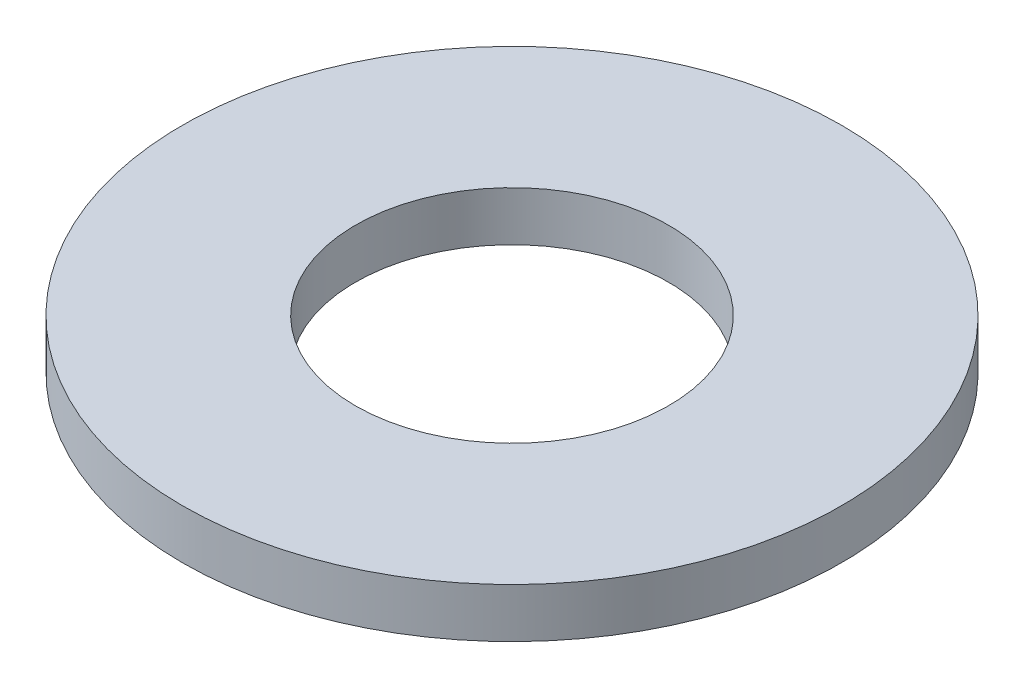
SolidWorks part; units mm, degrees
ref_plane "Front Plane" through (0, 0, 0) normal (0, 0, 1) x (1, 0, 0)
ref_plane "Top Plane" through (0, 0, 0) normal (0, 1, 0) x (1, 0, 0)
ref_plane "Right Plane" through (0, 0, 0) normal (1, 0, 0) x (0, 0, -1)
sketch "Sketch1" plane through (0, 0, 0) normal (0, 1, 0) x (1, 0, 0)
  circle A0 centre (0, 0) radius 100
  dimension "FLANGE_OD" = 200
extrude "Boss-Extrude1" add sketch "Sketch1" along normal blind 15
sketch "Sketch2" plane through (0, 0, 0) normal (0, 1, 0) x (1, 0, 0)
  circle A0 centre (0, 0) radius 47.5
  dimension "BORE_D" = 95
extrude "Cut-Extrude1" cut sketch "Sketch2" along normal through all
sketch "Sketch3" plane through (0, 15, 0) normal (0, 1, 0) x (1, 0, 0)
  circle A0 centre (0, 0) radius 35.8688 construction
  circle A1 centre (-35.8688, 0) radius 6.247
  dimension "BOLT_D" = 12.4939
  dimension "BOLT_PCD" = 71.7377
extrude "Cut-Extrude2" cut sketch "Sketch3" against normal blind 9.91 rebuild error yes
pattern_circular "CirPattern1" count 6 over 360 rebuild error yes
